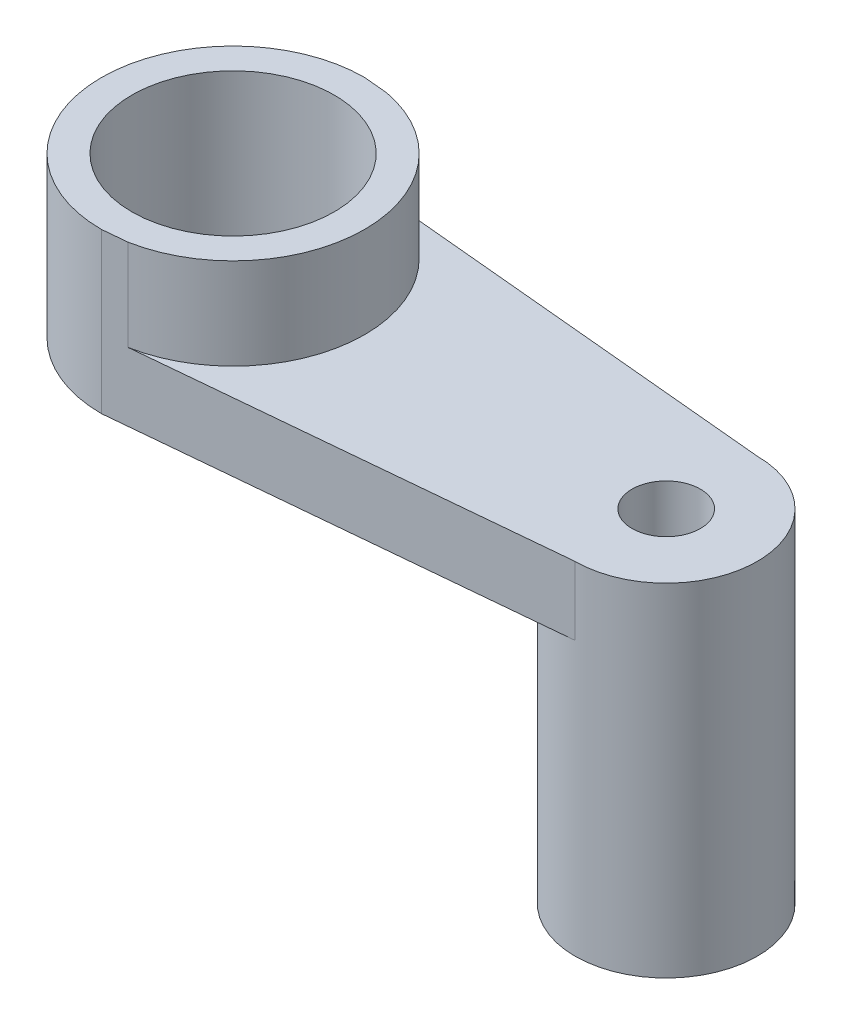
SolidWorks part; units mm, degrees
ref_plane "Front Plane" through (0, 0, 0) normal (0, 0, 1) x (1, 0, 0)
ref_plane "Top Plane" through (0, 0, 0) normal (0, 1, 0) x (1, 0, 0)
ref_plane "Right Plane" through (0, 0, 0) normal (1, 0, 0) x (0, 0, -1)
sketch "Sketch2" plane through (0, 0, 0) normal (0, 1, 0) x (1, 0, 0)
  line L0 (-38.953, 20.0286) -> (-0.953, 16.4763)
  line L1 (-38.953, -3.0613) -> (-0.953, 0.491)
  circle A0 centre (-38.953, 8.4836) radius 8.8807
  circle A1 centre (-38.953, 8.4836) radius 11.5449
  circle A2 centre (-0.953, 8.4836) radius 7.9926
  circle A3 centre (-0.953, 8.4836) radius 3
  point P10 (0, 0)
  point P11 (0, 0)
  dimension "D1" = 38
extrude "Boss-Extrude3" add sketch "Sketch2" along normal blind 14 contours L1 A1 L0 A0 region at (-37.9135, 0, -19.6034)
extrude "Boss-Extrude4" add sketch "Sketch2<4>" against normal blind 24 separate body contours A2 A3 region at (4.5388, 0, -13.9754)
sketch "Sketch2<4>" plane through (0, 0, 0) normal (0, 1, 0) x (1, 0, 0) same geometry as "Sketch2"
extrude "Boss-Extrude5" add sketch "Sketch2<5>" along normal blind 6 contours A2 A3 | A2 L0 A1 L1 region at (-18.7323, 0, -8.4836) region at (4.5388, 0, -13.9754)
sketch "Sketch2<5>" plane through (0, 0, 0) normal (0, 1, 0) x (1, 0, 0) same geometry as "Sketch2"
